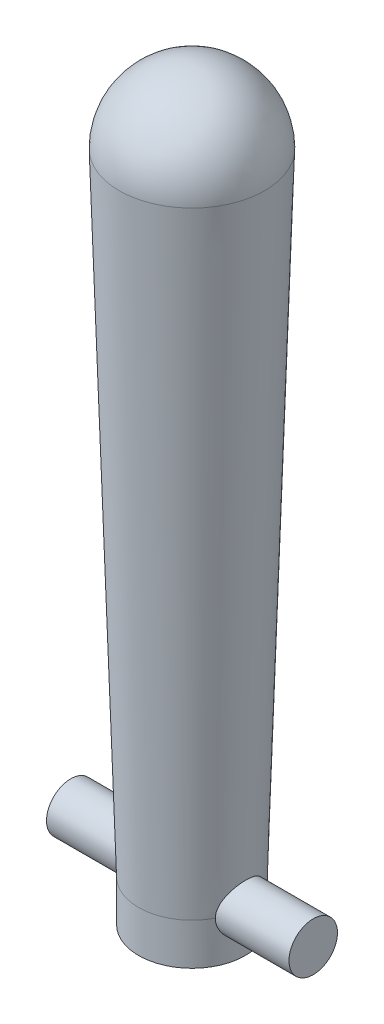
SolidWorks part; units mm, degrees
ref_plane "Plan de face" through (0, 0, 0) normal (0, 0, 1) x (1, 0, 0)
ref_plane "Plan de dessus" through (0, 0, 0) normal (0, 1, 0) x (1, 0, 0)
ref_plane "Plan de droite" through (0, 0, 0) normal (1, 0, 0) x (0, 0, -1)
sketch "Esquisse1" plane through (0, 0, 0) normal (1, 0, 0) x (0, 0, -1)
  line L0 (0, 0) -> (0, 17.181) construction
  line L1 (1.5, 13) -> (1.1, 0)
  line L2 (0, 0) -> (2.9133, 0) construction
  line L3 (3.98, 13) -> (-3.5933, 13) construction
  line L4 (1.1, 0) -> (1.1, -0.8578)
  line L5 (1.1, -0.8578) -> (0, -0.8578)
  line L6 (0, -0.8578) -> (0, 14.5)
  arc A0 (1.4972, 12.9078) -> (0, 14.5) centre (0, 13) ccw
  dimension "D1" = 2.2
  dimension "D2" = 3
  dimension "D3" = 13
revolve "Révolution1" add sketch "Esquisse1" angle 360 about L0 region at (0, 7.0969, -0.6484)
sketch "Esquisse2" plane through (0, 0, 0) normal (1, 0, 0) x (0, 0, -1)
  circle A0 centre (0, 0) radius 0.5
  dimension "D1" = 1
extrude "Boss.-Extru.1" add sketch "Esquisse2" along normal blind 2.5 and the other way blind 2.5
scale "Scale1" scale about centroid uniform scaling yes scale factor 0.64015
